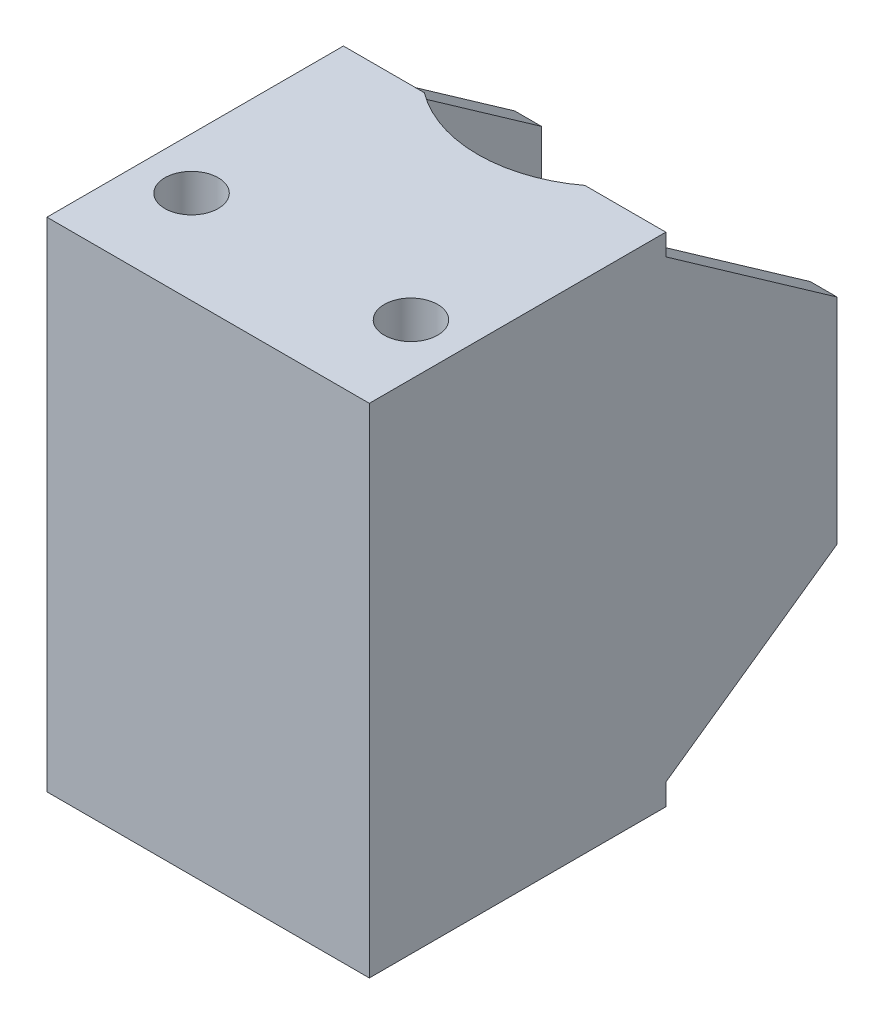
SolidWorks part; units mm, degrees
ref_plane "Front Plane" through (0, 0, 0) normal (0, 0, 1) x (1, 0, 0)
ref_plane "Top Plane" through (0, 0, 0) normal (0, 1, 0) x (1, 0, 0)
ref_plane "Right Plane" through (0, 0, 0) normal (1, 0, 0) x (0, 0, -1)
sketch "Sketch2" plane through (0, 0, 0) normal (0, 1, 0) x (1, 0, 0)
  line L0 (15.061, 0) -> (15.061, 37.7)
  line L1 (-12.561, 2.5) -> (12.561, 2.5)
  line L2 (-12.561, 2.5) -> (-12.561, 37.7)
  line L4 (12.561, 2.5) -> (12.561, 37.7)
  line L5 (15.061, 37.7) -> (12.561, 37.7)
  line L7 (-15.061, 37.7) -> (-15.061, 0)
  line L8 (-15.061, 0) -> (15.061, 0)
  line L10 (-15.061, 37.7) -> (-12.561, 37.7)
  point P4 (0, 2.5)
  point P12 (0, 0)
  dimension "D1" = 2.5
  dimension "D2" = 2.5
  dimension "D3" = 37.7
  dimension "D4" = 25.122
  dimension "D5" = 15.061
extrude "Boss-Extrude1" add sketch "Sketch2" along normal blind 32.5
sketch "Sketch4" plane through (0, 0, 0) normal (0, -1, 0) x (1, 0, 0)
  line L0 (-15.061, 0) -> (-15.061, -7.4438)
  line L8 (15.061, -7.4438) -> (15.061, 0)
  line L9 (15.061, 0) -> (-15.061, 0)
  line L10 (15.061, 0) -> (15.061, -37.7) construction
  line L13 (-15.061, -7.4438) -> (-15.061, -37.7)
  line L23 (-15.061, -37.7) -> (-12.561, -37.7)
  line L34 (-12.561, -37.7) -> (-12.561, -7.5)
  line L35 (-12.561, -2.5) -> (-12.561, -37.7) construction
  line L36 (-12.561, -7.5) -> (12.561, -7.5)
  line L37 (12.561, -37.7) -> (12.561, -2.5) construction
  line L38 (12.561, -7.5) -> (12.561, -37.7)
  line L39 (12.561, -37.7) -> (15.061, -37.7)
  line L40 (15.061, -37.7) -> (15.061, -7.4438)
  circle A2 centre (-10.2499, -4.95) radius 1.05
  circle A5 centre (10.2499, -4.95) radius 1.05
  dimension "D5" = 2.1
  dimension "D1" = 7.5
  dimension "D6" = 4.8111
  dimension "D7" = 4.95
  dimension "D8" = 4.8111
extrude "Boss-Extrude2" add sketch "Sketch4" along normal blind 2
sketch "Sketch7" plane through (0, -2, 0) normal (0, -1, 0) x (1, 0, 0)
  line L0 (-15.061, 0) -> (-15.061, -37.7)
  line L1 (-15.061, -37.7) -> (-12.561, -37.7)
  line L2 (-15.061, 0) -> (15.061, 0)
  line L4 (15.061, 0) -> (15.061, -37.7)
  line L5 (15.061, -37.7) -> (12.561, -37.7)
  line L6 (12.561, -37.7) -> (12.561, -7.5)
  line L7 (12.561, -7.5) -> (-12.561, -7.5)
  line L8 (-12.561, -7.5) -> (-12.561, -37.7)
  circle A2 centre (-10.2499, -4.95) radius 2.495
  circle A3 centre (10.2499, -4.95) radius 2.495
  dimension "D1" = 4.99
extrude "Wire spacing2" add sketch "Sketch7" along normal blind 3
sketch "Sketch8" plane through (0, -5, 0) normal (0, -1, 0) x (1, 0, 0)
  line L0 (-15.061, 0) -> (-15.061, -37.7)
  line L1 (-15.061, -37.7) -> (15.061, -37.7)
  line L2 (15.061, -37.7) -> (15.061, 0) construction
  line L3 (12.561, -37.7) -> (15.061, -37.7) construction
  line L4 (-15.061, 0) -> (15.061, 0)
  line L6 (15.061, 0) -> (15.061, -37.7)
  circle A0 centre (-10.2499, -4.95) radius 2.495
  circle A1 centre (10.2499, -4.95) radius 2.495
  circle A2 centre (10.2499, -4.95) radius 2.495 construction
  circle A3 centre (-10.2499, -4.95) radius 2.495 construction
extrude "Boss-Extrude6" add sketch "Sketch8" along normal blind 2
sketch "Sketch5" plane through (0, 32.5, 0) normal (0, 1, 0) x (1, 0, 0)
  line L0 (-7.5, 10) -> (-7.5, 2.5)
  line L9 (12.561, 2.5) -> (-12.561, 2.5) construction
  line L11 (-10.2499, 12) -> (-7.5, 10)
  line L13 (-15.061, 0) -> (15.061, 0) construction
  line L15 (-15.061, 0) -> (-15.061, 37.7)
  line L17 (10.2499, 12) -> (7.5, 10)
  line L20 (15.061, 0) -> (15.061, 37.7)
  line L21 (-7.5, 2.5) -> (7.5, 2.5)
  line L22 (7.5, 2.5) -> (7.5, 10)
  line L23 (-15.061, 0) -> (15.061, 0)
  line L24 (-10.2499, 12) -> (-12.561, 12)
  line L25 (-12.561, 37.7) -> (-12.561, 7.5) construction
  line L26 (-12.561, 12) -> (-12.561, 37.7)
  line L27 (-12.561, 37.7) -> (-15.061, 37.7)
  line L30 (15.061, 37.7) -> (12.561, 37.7)
  line L31 (12.561, 37.7) -> (12.561, 12)
  line L32 (12.561, 7.5) -> (12.561, 37.7) construction
  line L33 (12.561, 12) -> (10.2499, 12)
  circle A0 centre (-10.2499, 4.95) radius 1.05 construction
  circle A1 centre (-10.2499, 8.7) radius 1.05
  circle A2 centre (10.2499, 8.7) radius 1.05
  dimension "D4" = 0
  dimension "D7" = 8.7
  dimension "D1" = 12
  dimension "D2" = 7.561
  dimension "D3" = 20.4998
  dimension "D5" = 10
  dimension "D6" = 7.561
extrude "Boss-Extrude3" add sketch "Sketch5" along normal blind 2
sketch "Sketch9" plane through (0, 34.5, 0) normal (0, 1, 0) x (1, 0, 0)
  line L0 (-15.061, 0) -> (-15.061, 37.7)
  line L1 (-15.061, 37.7) -> (-12.561, 37.7)
  line L2 (-12.561, 37.7) -> (-12.561, 12)
  line L3 (-12.561, 12) -> (-10.2499, 12)
  line L4 (-10.2499, 12) -> (-7.5, 10)
  line L5 (-7.5, 10) -> (-7.5, 2.5)
  line L6 (-7.5, 2.5) -> (7.5, 2.5)
  line L7 (7.5, 2.5) -> (7.5, 10)
  line L8 (7.5, 10) -> (10.2499, 12)
  line L9 (10.2499, 12) -> (7.5, 10) construction
  line L10 (10.2499, 12) -> (12.561, 12)
  line L11 (12.561, 7.5) -> (12.561, 37.7) construction
  line L12 (12.561, 12) -> (12.561, 37.7)
  line L13 (12.561, 37.7) -> (15.061, 37.7)
  line L14 (15.061, 0) -> (15.061, 37.7) construction
  line L15 (15.061, 37.7) -> (12.561, 37.7) construction
  line L16 (15.061, 37.7) -> (15.061, 0)
  line L17 (15.061, 0) -> (-15.061, 0)
  circle A0 centre (-10.2499, 8.7) radius 2.495
  circle A1 centre (10.2499, 8.7) radius 2.495
  dimension "D1" = 4.99
extrude "Wire spacing1" add sketch "Sketch9" along normal blind 3
sketch "Sketch10" plane through (0, 37.5, 0) normal (0, 1, 0) x (1, 0, 0)
  line L1 (-15.061, 37.7) -> (15.061, 37.7)
  line L2 (-15.061, 37.7) -> (-15.061, 0)
  line L3 (-15.061, 0) -> (15.061, 0)
  line L4 (15.061, 37.7) -> (15.061, 0)
  circle A0 centre (-10.2499, 8.7) radius 2.495
  circle A1 centre (10.2499, 8.7) radius 2.495
  circle A2 centre (-10.2499, 8.7) radius 2.495 construction
  circle A3 centre (10.2499, 8.7) radius 2.495 construction
extrude "Boss-Extrude8" add sketch "Sketch10" along normal blind 2
sketch "Sketch11" plane through (0, 39.5, 0) normal (0, 1, 0) x (1, 0, 0)
  line L0 (15.061, 37.7) -> (-15.061, 37.7) construction
  circle A0 centre (0, 37.7) radius 12.5
  dimension "D1" = 25
extrude "Cut-Extrude1" cut sketch "Sketch11" against normal through all
ref_plane "Box Mid Plane" through (0, 16.25, 0) normal (0, 1, 0) x (1, 0, 0)
sketch "Sketch18" plane through (0, 39.5, 0) normal (0, 1, 0) x (1, 0, 0)
  line L1 (-15.061, 37.7) -> (-5.061, 37.7)
  line L2 (-15.061, 37.7) -> (-15.061, 27.7)
  line L3 (-15.061, 27.7) -> (-5.061, 27.7)
  line L4 (-5.061, 37.7) -> (-5.061, 27.7)
  line L5 (15.061, 37.7) -> (5.061, 37.7)
  line L6 (15.061, 37.7) -> (15.061, 27.7)
  line L7 (15.061, 27.7) -> (5.061, 27.7)
  line L8 (5.061, 37.7) -> (5.061, 27.7)
  dimension "D1" = 10
  dimension "D2" = 10
extrude "Cut-Extrude4" cut sketch "Sketch18" against normal through all
sketch "Sketch19" plane through (-15.061, 0, 0) normal (-1, 0, 0) x (0, 0, 1)
  line L0 (-27.7, 37.5) -> (-43.7, 26.25)
  line L1 (-43.7, 26.25) -> (-43.7, 6.25)
  line L2 (-43.7, 6.25) -> (-27.7, -5)
  line L3 (-27.7, -5) -> (-27.7, 37.5)
  point P3 (-27.7, 16.25)
  point P7 (-43.7, 16.25)
  dimension "D1" = 20
  dimension "D2" = 16
extrude "Boss-Extrude10" add sketch "Sketch19" against normal up to surface (2.5 mm away) up to face at (-12.561, 16.25, -12.425)
sketch "Sketch20" plane through (15.061, 0, 0) normal (1, 0, 0) x (0, 0, -1)
  line L0 (27.7, 37.5) -> (43.7, 26.25)
  line L1 (43.7, 26.25) -> (43.7, 6.25)
  line L2 (43.7, 6.25) -> (27.7, -5)
  line L3 (27.7, -5) -> (27.7, 37.5)
extrude "Boss-Extrude11" add sketch "Sketch20" against normal up to surface (2.5 mm away) up to face at (12.561, 16.25, -12.425)
